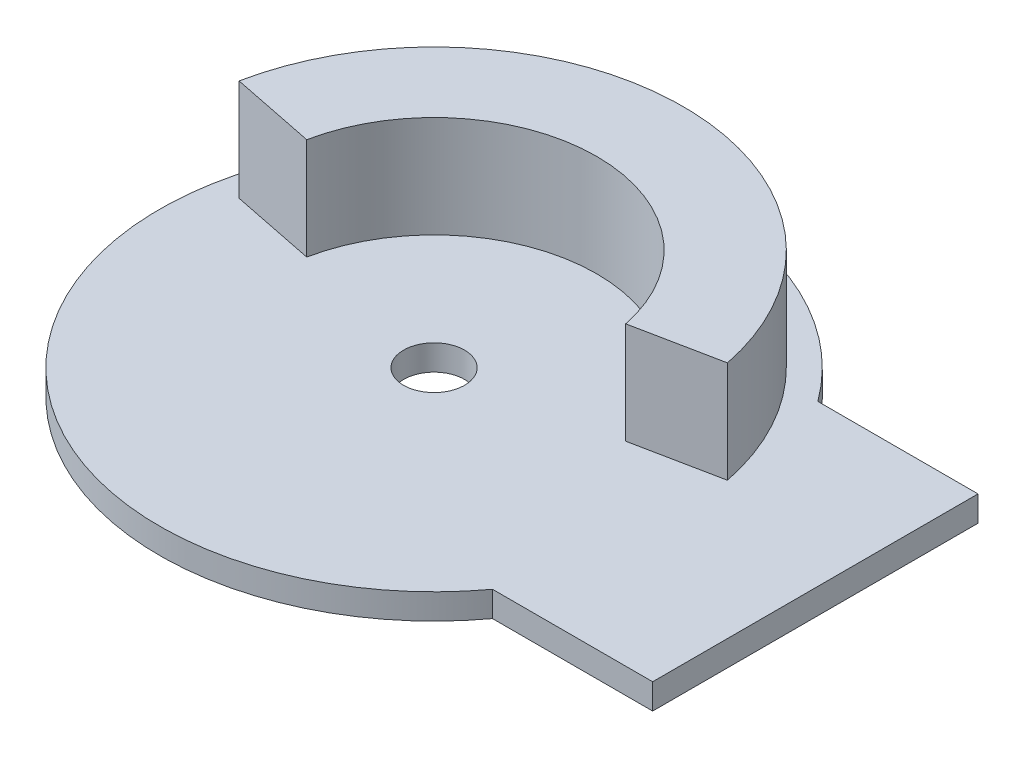
SolidWorks part; units mm, degrees
ref_plane "Front Plane" through (0, 0, 0) normal (0, 0, 1) x (1, 0, 0)
ref_plane "Top Plane" through (0, 0, 0) normal (0, 1, 0) x (1, 0, 0)
ref_plane "Right Plane" through (0, 0, 0) normal (1, 0, 0) x (0, 0, -1)
sketch "Sketch1" plane through (0, 0, 0) normal (0, 1, 0) x (1, 0, 0)
  line L0 (-55, 0) -> (55, 0) construction
  line L1 (-24.0173, 4.8395) -> (-20.7184, 21.2108) construction
  line L2 (-24.0173, 4.8395) -> (-15.6847, 3.1605)
  line L3 (0, -55) -> (0, 55) construction
  line L4 (24.0173, 4.8395) -> (15.6847, 3.1605)
  line L5 (-23.9844, 5) -> (23.9844, 5) construction
  circle A0 centre (0, 0) radius 16 construction
  circle A1 centre (0, 0) radius 24.5 construction
  arc A2 (-24.0173, 4.8395) -> (24.0173, 4.8395) centre (0, 0) cw
  arc A3 (-15.6847, 3.1605) -> (15.6847, 3.1605) centre (0, 0) cw
  point P20 (-19.851, 4)
  dimension "D1" = 32
  dimension "D2" = 49
  dimension "D3" = 1
  dimension "D4" = 5
extrude "Boss-Extrude1" add sketch "Sketch1" along normal blind 10 contours A2 L4 A3 L2
sketch "Sketch2" plane through (0, 0, 0) normal (0, -1, 0) x (1, 0, 0)
  line L1 (37.5, -16) -> (37.5, 16)
  line L3 (21.7486, -16) -> (37.5, -16)
  line L5 (21.7486, 16) -> (37.5, 16)
  line L6 (0, -55) -> (0, 55) construction
  circle A1 centre (0, 0) radius 27 construction
  circle A2 centre (0, 0) radius 3
  arc A3 (0, -27) -> (0, 27) centre (0, 0) cw
  circle A4 centre (0, 0) radius 16 construction
  arc A5 (21.7486, -16) -> (0, -27) centre (0, 0) cw
  arc A6 (0, 27) -> (21.7486, 16) centre (0, 0) cw
  dimension "D1" = 54
  dimension "D2" = 6
  dimension "D3" = 37.5
extrude "Boss-Extrude2" add sketch "Sketch2" along normal blind 2.5
sketch "Sketch4" plane through (0, 0, 0) normal (0, 1, 0) x (1, 0, 0)
  line L0 (37.5, -16) -> (21.7486, -16) construction
  line L1 (37.5, -16) -> (35, -16)
  line L2 (37.5, -16) -> (37.5, 16)
  line L3 (37.5, 16) -> (35, 16)
  line L4 (35, -16) -> (35, 16)
  line L5 (21.7486, 16) -> (37.5, 16) construction
  dimension "D1" = 2.5
  dimension "D2" = 35
extrude "Boss-Extrude3" [suppressed] add sketch "Sketch4" along normal blind 60
sketch "Sketch5" [suppressed] plane through (37.5, 0, 0) normal (1, 0, 0) x (0, 0, -1)
  line L0 (16, 60) -> (-16, -2.5) construction
  line L1 (-16, -2.5) -> (16, -2.5) construction
  line L2 (16, -2.5) -> (-16, 60) construction
  circle A0 centre (0, 28.75) radius 5
  dimension "D1" = 10
extrude "Cut-Extrude1" [suppressed] cut sketch "Sketch5" against normal blind 10
ref_axis "Axis1" [suppressed] through (35, 28.75, 0) along (1, 0, 0)
ref_plane "Plane1" [suppressed] through (0, 28.75, 0) normal (0, 1, 0) x (1, 0, 0)
